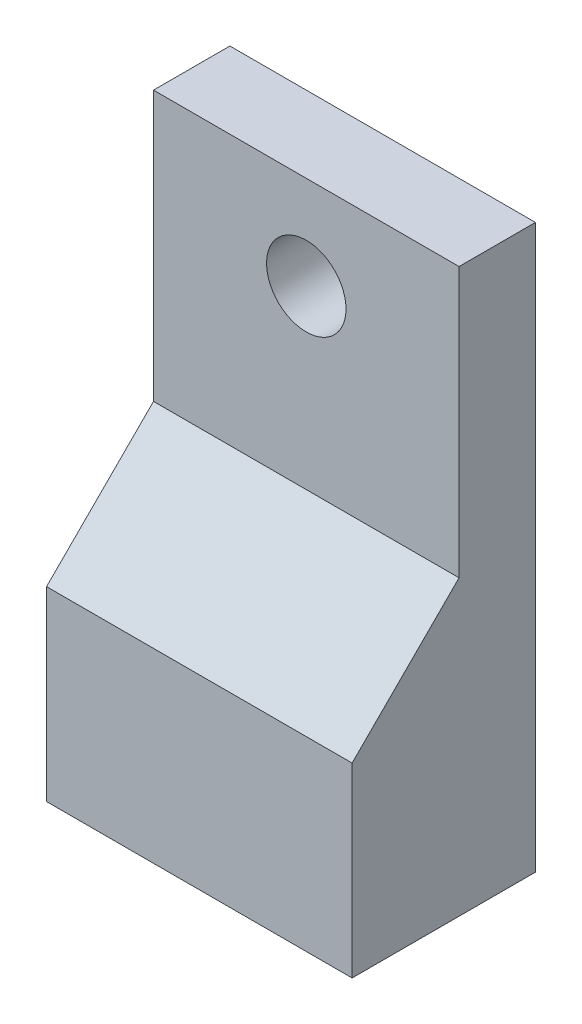
SolidWorks part; units mm, degrees
ref_plane "Přední rovina" through (0, 0, 0) normal (0, 0, 1) x (1, 0, 0)
ref_plane "Horní rovina" through (0, 0, 0) normal (0, 1, 0) x (1, 0, 0)
ref_plane "Pravá rovina" through (0, 0, 0) normal (1, 0, 0) x (0, 0, -1)
sketch "Skica1" plane through (0, 0, 0) normal (0, 0, 1) x (1, 0, 0)
  line L0 (24.5243, -340) -> (24.5243, 0) construction
  line L1 (4.5243, -315.7) -> (24.5243, -315.7)
  line L2 (4.5243, -315.7) -> (4.5243, -278.8699)
  line L3 (4.5243, -278.8699) -> (24.5243, -278.8699)
  line L4 (24.5243, -315.7) -> (24.5243, -278.8699)
  circle A0 centre (14.5243, -284.9815) radius 2.6
  dimension "D1" = 5.2
extrude "Přidat vysunutím1" add sketch "Skica1" along normal blind 5
sketch "Skica2" plane through (0, 0, 5) normal (0, 0, 1) x (1, 0, 0)
  line L0 (4.5243, -278.8699) -> (4.5243, -315.7) construction
  line L1 (24.5243, -315.7) -> (4.5243, -315.7)
  line L2 (24.5243, -315.7) -> (24.5243, -296.5156)
  line L3 (24.5243, -296.5156) -> (4.5243, -296.5156)
  line L4 (4.5243, -315.7) -> (4.5243, -296.5156)
extrude "Přidat vysunutím2" add sketch "Skica2" along normal up to surface (7 mm away)
chamfer "Zkosení1" distance 7 angle 45 1 edges at (14.5243, -296.5156, 12)
